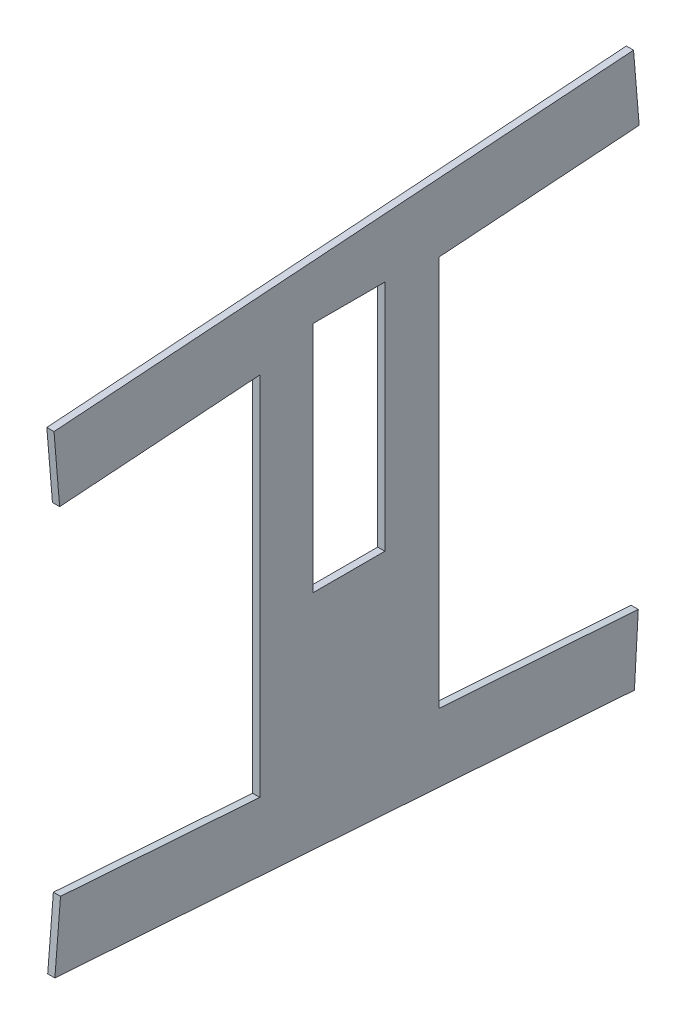
SolidWorks part; units mm, degrees
ref_plane "Front Plane" through (0, 0, 0) normal (0, 0, 1) x (1, 0, 0)
ref_plane "Top Plane" through (0, 0, 0) normal (0, 1, 0) x (1, 0, 0)
ref_plane "Right Plane" through (0, 0, 0) normal (1, 0, 0) x (0, 0, -1)
sketch "Sketch1" plane through (0, 0, 0) normal (1, 0, 0) x (0, 0, -1)
  line L12 (-23.4265, -51) -> (-23.4265, 51)
  line L13 (-23.4265, 51) -> (-79.2292, 47.0979)
  line L14 (-79.2292, 47.0979) -> (-80.8027, 66.0343)
  line L15 (-80.8027, 66.0343) -> (80.8027, 77.3348)
  line L16 (80.8027, 77.3348) -> (82.3762, 58.3984)
  line L17 (82.3762, 58.3984) -> (26.5735, 54.4963)
  line L18 (26.5735, 54.4963) -> (26.5735, -54.4963)
  line L19 (26.5735, -54.4963) -> (82.1281, -58.3811)
  line L20 (82.1281, -58.3811) -> (81.0508, -77.3522)
  line L21 (81.0508, -77.3522) -> (-80.5546, -66.0516)
  line L22 (-80.5546, -66.0516) -> (-78.9811, -47.1152)
  line L23 (-78.9811, -47.1152) -> (-23.4265, -51)
  point P3 (-98.9164, -68.6006)
  point P13 (0, 71.6845)
  point P15 (26.5735, 0)
  dimension "D1" = 19
  dimension "D2" = 19
  dimension "D3" = 89.25
  dimension "D4" = 89.25
  dimension "D5" = 94
  dimension "D6" = 94
  dimension "D7" = 50
  dimension "D8" = 162
  dimension "D9" = 162
  dimension "D10" = 102
extrude "Boss-Extrude1" add sketch "Sketch1" along normal blind 2
sketch "Sketch2" plane through (2, 0, 0) normal (1, 0, 0) x (0, 0, -1)
  line L1 (-8.5383, 56.0008) -> (11.4617, 56.0008)
  line L2 (-8.5383, 56.0008) -> (-8.5383, -8.9992)
  line L3 (-8.5383, -8.9992) -> (11.4617, -8.9992)
  line L4 (11.4617, 56.0008) -> (11.4617, -8.9992)
  line L5 (-8.5383, 56.0008) -> (11.4617, -8.9992) construction
  line L6 (-8.5383, -8.9992) -> (11.4617, 56.0008) construction
  point P0 (1.4617, 23.5008)
  point P5 (1.7885, 25.3902)
  point P6 (1.6466, 25.7063)
  point P7 (1.7756, 23.8461)
  point P8 (0, 0)
  point P9 (1.4617, 23.4122)
  point P10 (1.5503, 24.6524)
  point P11 (1.4617, 23.5008)
  dimension "D1" = 20
  dimension "D2" = 65
extrude "Cut-Extrude1" cut sketch "Sketch2" against normal through all
